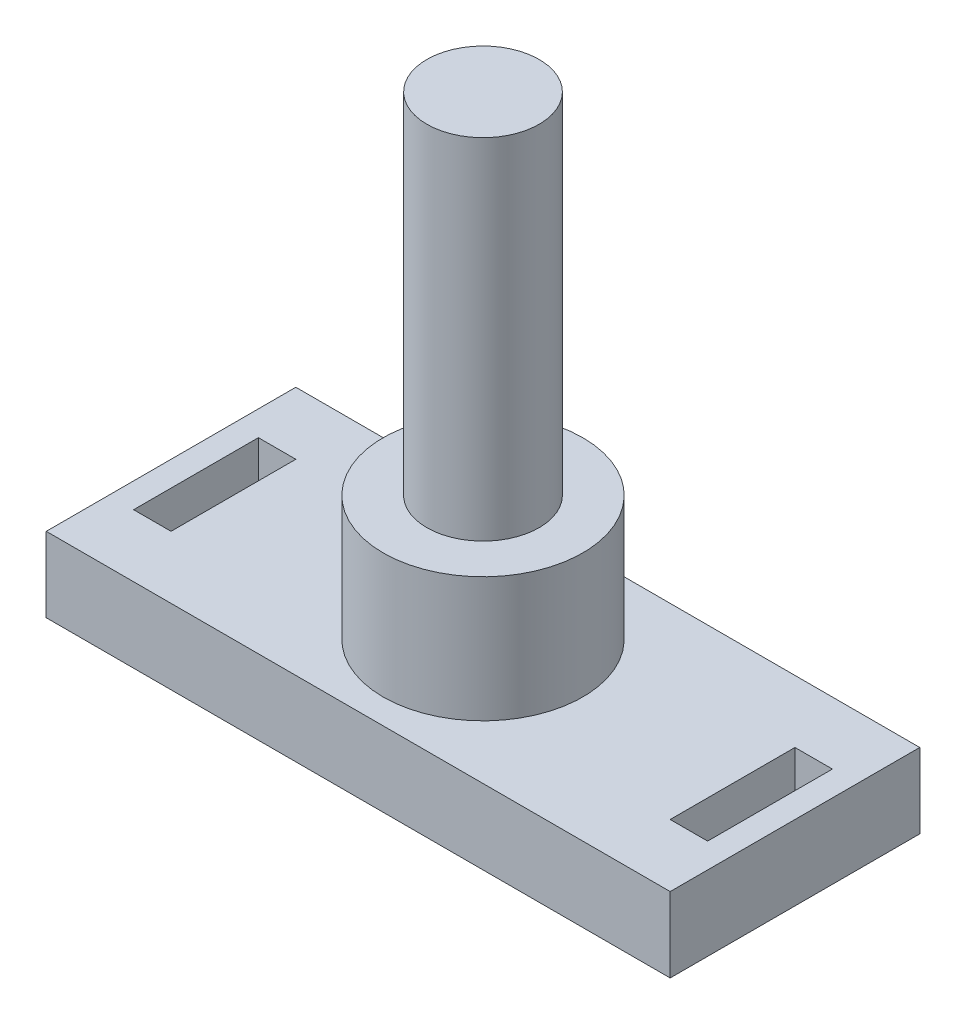
SolidWorks part; units mm, degrees
ref_plane "Front Plane" through (0, 0, 0) normal (0, 0, 1) x (1, 0, 0)
ref_plane "Top Plane" through (0, 0, 0) normal (0, 1, 0) x (1, 0, 0)
ref_plane "Right Plane" through (0, 0, 0) normal (1, 0, 0) x (0, 0, -1)
sketch "Sketch1" plane through (0, 0, 0) normal (0, 1, 0) x (1, 0, 0)
  circle A0 centre (0, 0) radius 2.25
  dimension "D1" = 4.5
extrude "Boss-Extrude1" add sketch "Sketch1" along normal blind 14 contours A0
sketch "Sketch2" plane through (0, 0, 0) normal (0, -1, 0) x (1, 0, 0)
  circle A0 centre (0, 0) radius 4
  dimension "D1" = 8
extrude "Boss-Extrude2" add sketch "Sketch2" along normal blind 5
sketch "Sketch3" plane through (0, -5, 0) normal (0, -1, 0) x (1, 0, 0)
  line L1 (-12.5, -5) -> (12.5, -5)
  line L2 (-12.5, -5) -> (-12.5, 5)
  line L3 (-12.5, 5) -> (12.5, 5)
  line L4 (12.5, -5) -> (12.5, 5)
  circle A0 centre (0, 0) radius 4 construction
  dimension "D3" = 5
  dimension "D1" = 25
  dimension "D2" = 10
  dimension "D4" = 12.5
extrude "Boss-Extrude3" add sketch "Sketch3" along normal blind 3 contours L2 L3 L4 L1
sketch "Sketch4" plane through (0, -8, 0) normal (0, -1, 0) x (1, 0, 0)
  line L0 (10, 0) -> (-10, 0) construction
  line L1 (12.5, -5) -> (12.5, 5) construction
  line L2 (-10, 2.5) -> (-11.5, 2.5)
  line L3 (-10, 2.5) -> (-10, -2.5)
  line L4 (-10, -2.5) -> (-11.5, -2.5)
  line L5 (-11.5, 2.5) -> (-11.5, -2.5)
  line L6 (10, 2.5) -> (11.5, 2.5)
  line L7 (10, 2.5) -> (10, -2.5)
  line L8 (10, -2.5) -> (11.5, -2.5)
  line L9 (11.5, 2.5) -> (11.5, -2.5)
  line L10 (-12.5, -5) -> (12.5, -5) construction
  point P4 (0, 0)
  dimension "D1" = 20
  dimension "D2" = 5
  dimension "D3" = 2.5
  dimension "D4" = 5
  dimension "D5" = 2.5
  dimension "D6" = 1.5
  dimension "D7" = 1.5
extrude "Cut-Extrude1" cut sketch "Sketch4" against normal blind 3
